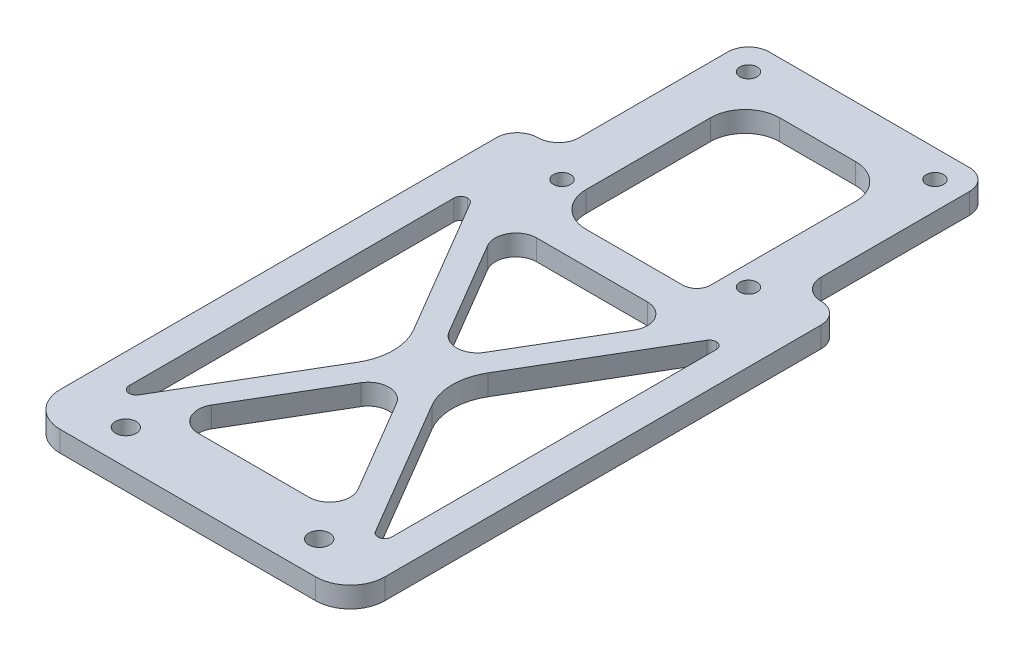
SolidWorks part; units mm, degrees
material "Thornel Mat VMA"
ref_plane "前视基准面" through (0, 0, 0) normal (0, 0, 1) x (1, 0, 0)
ref_plane "上视基准面" through (0, 0, 0) normal (0, 1, 0) x (1, 0, 0)
ref_plane "右视基准面" through (0, 0, 0) normal (1, 0, 0) x (0, 0, -1)
other "Configuration Table"
sketch "草图1" plane through (0, 0, 0) normal (0, 1, 0) x (1, 0, 0)
  line L0 (0, 0) -> (0, 40.9092) construction
  line L1 (-23.5, -20) -> (23.5, -20)
  line L2 (-23.5, -20) -> (-23.5, 20)
  line L3 (-23.5, 20) -> (23.5, 20)
  line L4 (23.5, -20) -> (23.5, 20)
  line L5 (-23.5, -20) -> (23.5, 20) construction
  line L6 (-23.5, 20) -> (23.5, -20) construction
  line L7 (0, 0) -> (66.2179, 0) construction
  line L16 (0, 0) -> (0, -21.1131) construction
  line L17 (-10.5, -8) -> (10.5, -8)
  line L18 (10.5, -8) -> (10.5, -18)
  line L19 (10.5, -18) -> (-10.5, -18)
  line L20 (-10.5, -8) -> (-10.5, -18)
  line L21 (-23.5, -20) -> (-23.5, -86.16)
  line L22 (-23.5, -86.16) -> (23.5, -86.16)
  line L23 (23.5, -86.16) -> (23.5, -20)
  line L24 (0, -8) -> (0, -18)
  point P0 (0, 0)
  point P23 (0, -18)
  point P24 (0, -8)
  dimension "D1" = 47
  dimension "D2" = 40
  dimension "D6" = 21
  dimension "D7" = 10
  dimension "D8" = 8
  dimension "D9" = 86.16
extrude "凸台-拉伸1" add sketch "草图1" along normal blind 3 contours L1 L4 L3 L2 L20 L17 L18 L19 | L22 L23 L1 L21 | L24 L17 L20 L19 region at (0, 0, -1.6347) region at (0, 0, 53.08) region at (-5.25, 0, 13)
sketch "草图4" plane through (0, 3, 0) normal (0, 1, 0) x (1, 0, 0)
  line L0 (0, 0) -> (0, -81.16) construction
  line L2 (-23.5, -81.16) -> (23.5, -81.16)
  line L3 (-23.5, -86.16) -> (-23.5, 20) construction
  line L4 (23.5, -86.16) -> (23.5, 20) construction
  line L5 (23.5, -81.16) -> (23.5, -86.16)
  line L6 (23.5, -86.16) -> (-23.5, -86.16)
  line L7 (-23.5, -86.16) -> (-23.5, -81.16)
  circle A8 centre (-14, -76.16) radius 1.5
  circle A9 centre (14, -76.16) radius 1.5
  dimension "D1" = 3
  dimension "D2" = 28
  dimension "D3" = 5
  dimension "D7" = 5
extrude "切除-拉伸2" cut sketch "草图4" against normal blind 4
sketch "草图9" plane through (0, 3, 0) normal (0, 1, 0) x (1, 0, 0)
  line L0 (0, -81.16) -> (0, 21.7085) construction
  line L1 (23.5, -81.16) -> (-23.5, -81.16) construction
  line L2 (0, -47.16) -> (69.6905, -47.16) construction
  line L3 (13.2589, -22.66) -> (0, -45.16)
  line L4 (-19, -71.66) -> (19, -71.66)
  line L5 (-19, -71.66) -> (-19, -22.66)
  line L6 (-19, -22.66) -> (19, -22.66)
  line L7 (19, -71.66) -> (19, -22.66)
  line L8 (-19, -71.66) -> (19, -22.66) construction
  line L9 (-19, -22.66) -> (19, -71.66) construction
  line L10 (17.4375, -22.66) -> (3, -47.16)
  line L11 (-17.4375, -22.66) -> (-3, -47.16)
  line L12 (-13.2589, -22.66) -> (0, -45.16)
  line L13 (17.4375, -71.66) -> (3, -47.16)
  line L14 (13.2589, -71.66) -> (0, -49.16)
  line L15 (-13.2589, -71.66) -> (0, -49.16)
  line L16 (-17.4375, -71.66) -> (-3, -47.16)
  dimension "D1" = 38
  dimension "D2" = 49
  dimension "D3" = 34
  dimension "D4" = 2
  dimension "D5" = 3
  dimension "D6" = 3.6
sketch "草图10" plane through (0, 3, 0) normal (0, 1, 0) x (1, 0, 0)
  line L0 (0, 0) -> (30.3875, 0) construction
  line L1 (-16, -16) -> (16, -16) construction
  line L2 (-16, -16) -> (-16, 16) construction
  line L3 (-16, 16) -> (16, 16) construction
  line L4 (16, -16) -> (16, 16) construction
  line L5 (-16, -16) -> (16, 16) construction
  line L6 (-16, 16) -> (16, -16) construction
  line L7 (0, 0) -> (0, 24.3675) construction
  circle A0 centre (13.5, 13.5) radius 1.25
  circle A1 centre (13.5, -13.5) radius 1.25
  circle A2 centre (-13.5, -13.5) radius 1.25
  circle A3 centre (-13.5, 13.5) radius 1.25
  point P0 (0, 0)
  dimension "D3" = 2.5
  dimension "D4" = 27
  dimension "D5" = 27
  dimension "D1" = 32
  dimension "D2" = 32
extrude "切除-拉伸4" cut sketch "草图10" against normal blind 10
sketch "草图16" plane through (0, 3, 0) normal (0, 1, 0) x (1, 0, 0)
  line L0 (-17.5, 20) -> (-17.5, -10)
  line L1 (-23.5, 20) -> (23.5, 20) construction
  line L2 (-17.5, -10) -> (-23.5, -10)
  line L3 (-23.5, -81.16) -> (-23.5, 20) construction
  line L4 (-23.5, -10) -> (-23.5, 20)
  line L5 (-23.5, 20) -> (-17.5, 20)
  line L7 (0, 0) -> (0, 29.5698) construction
  line L8 (-16, 16) -> (16, -16) construction
  line L9 (23.5, -10) -> (23.5, 20)
  line L10 (17.5, -10) -> (23.5, -10)
  line L11 (17.5, 20) -> (17.5, -10)
  line L12 (23.5, 20) -> (17.5, 20)
  line L13 (-17.5, 20) -> (17.5, 20)
  line L14 (-17.5, 17.5) -> (17.5, 17.5)
  circle A0 centre (-13.5, 13.5) radius 1.25 construction
  line M12 (23.5, -81.16) -> (23.5, 20)
  line M13 (23.5, 20) -> (-23.5, 20)
  line M14 (-23.5, 20) -> (-23.5, -81.16)
  dimension "D1" = 4
  dimension "D2" = 30
  dimension "D3" = 4
extrude "切除-拉伸5" cut sketch "草图16" against normal blind 10 contours L2 L0 M13 M14 | L11 L10 M13 M12 | L7 L14 L11 M13 | L14 L7 L13 L0 region at (-8.75, 3, -18.75) region at (-20.5, 3, -5) region at (8.75, 3, -18.75) region at (20.5, 3, -5)
fillet "圆角1" radius 3 6 edges at (-17.5, 1.5, -17.5) (17.5, 1.5, -17.5) (23.5, 1.5, 10) (-23.5, 1.5, 10) (17.5, 1.5, 10) (-17.5, 1.5, 10)
extrude "切除-拉伸7" cut sketch "草图9" against normal blind 10 contours L4 L16 L11 L6 L5 | L6 L12 L3 | L13 L4 L7 L6 L10 | L15 L4 L14 region at (0, 3, 30.16) region at (13.6203, 3, 47.16) region at (-13.6203, 3, 47.16) region at (0, 3, 64.16)
fillet "圆角2" radius 1 8 edges at (-17.4375, 1.5, 71.66) (-19, 1.5, 71.66) (17.4375, 1.5, 71.66) (19, 1.5, 71.66) (19, 1.5, 22.66) (17.4375, 1.5, 22.66) (-17.4375, 1.5, 22.66) (-19, 1.5, 22.66)
fillet "圆角3" radius 8 2 edges at (3, 1.5, 47.16) (-3, 1.5, 47.16)
fillet "圆角4" radius 3 6 edges at (-13.2589, 1.5, 71.66) (13.2589, 1.5, 71.66) (0, 1.5, 49.16) (0, 1.5, 45.16) (13.2589, 1.5, 22.66) (-13.2589, 1.5, 22.66)
fillet "圆角5" radius 5 2 edges at (-23.5, 1.5, 81.16) (23.5, 1.5, 81.16)
sketch "草图17" plane through (0, 3, 0) normal (0, 1, 0) x (1, 0, 0)
  line L0 (-10.5, -10) -> (-10.5, -18)
  line L1 (-10.5, -10) -> (10.5, -10)
  line L2 (-10.5, -10) -> (-10.5, 10)
  line L3 (-10.5, 10) -> (10.5, 10)
  line L4 (10.5, -10) -> (10.5, 10)
  line L5 (-10.5, -10) -> (10.5, 10) construction
  line L6 (-10.5, 10) -> (10.5, -10) construction
  line L7 (-10.5, -18) -> (10.5, -18)
  line L8 (10.5, -18) -> (10.5, -10)
  point P0 (0, 0)
  dimension "D1" = 21
  dimension "D2" = 20
  dimension "D3" = 8
extrude "切除-拉伸8" cut sketch "草图17" against normal blind 10 contours L1 L4 L3 L2 | L7 L8 L1 L0 region at (0, 3, 14) region at (0, 3, 0)
fillet "圆角6" radius 5 3 edges at (10.5, 1.5, -10) (-10.5, 1.5, -10) (-10.5, 1.5, 18)
fillet "圆角7" radius 2 1 edges at (10.5, 1.5, 18)
